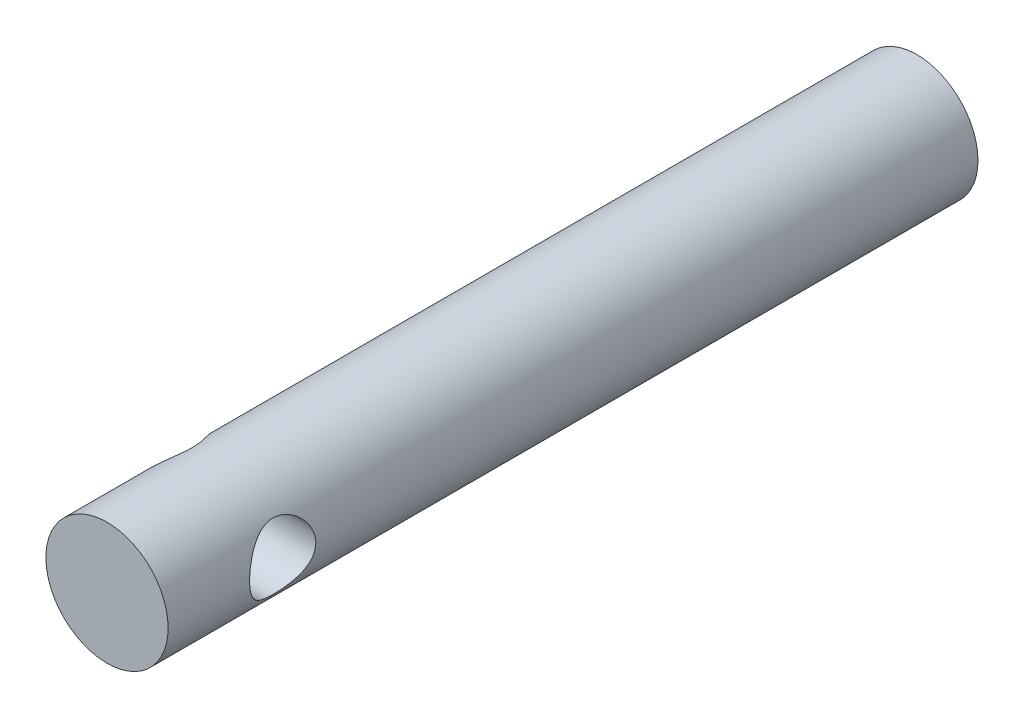
SolidWorks part; units mm, degrees
ref_plane "Front Plane" through (0, 0, 0) normal (0, 0, 1) x (1, 0, 0)
ref_plane "Top Plane" through (0, 0, 0) normal (0, 1, 0) x (1, 0, 0)
ref_plane "Right Plane" through (0, 0, 0) normal (1, 0, 0) x (0, 0, -1)
sketch "Sketch1" plane through (0, 0, 0) normal (0, 0, 1) x (1, 0, 0)
  circle A0 centre (0, 0) radius 4
extrude "Boss-Extrude1" add sketch "Sketch1" along normal blind 53.0026
sketch "Sketch2" plane through (0, 0, 0) normal (1, 0, 0) x (0, 0, -1)
  line L0 (-53.0026, -4) -> (0, -4) construction
  line L1 (-53.0026, 4) -> (-38.0026, 4) construction
  line L2 (-53.0026, 4) -> (-53.0026, -4) construction
  line L3 (-53.0026, -4) -> (-38.0026, -4) construction
  line L4 (-38.0026, 4) -> (-38.0026, -4) construction
  line L5 (-53.0026, 4) -> (-38.0026, -4) construction
  line L6 (-38.0026, 4) -> (-53.0026, -4) construction
  circle A0 centre (-45.5026, 0) radius 2.165
  dimension "D2" = 4.33
  dimension "D1" = 15
extrude "Cut-Extrude1" cut sketch "Sketch2" against normal mid plane 18
sketch "Sketch4" plane through (0, 0, 0) normal (1, 0, 0) x (0, 0, -1)
  circle A0 centre (-45.5026, 0) radius 3.5
extrude "Cut-Extrude2" cut sketch "Sketch4" against normal through all
